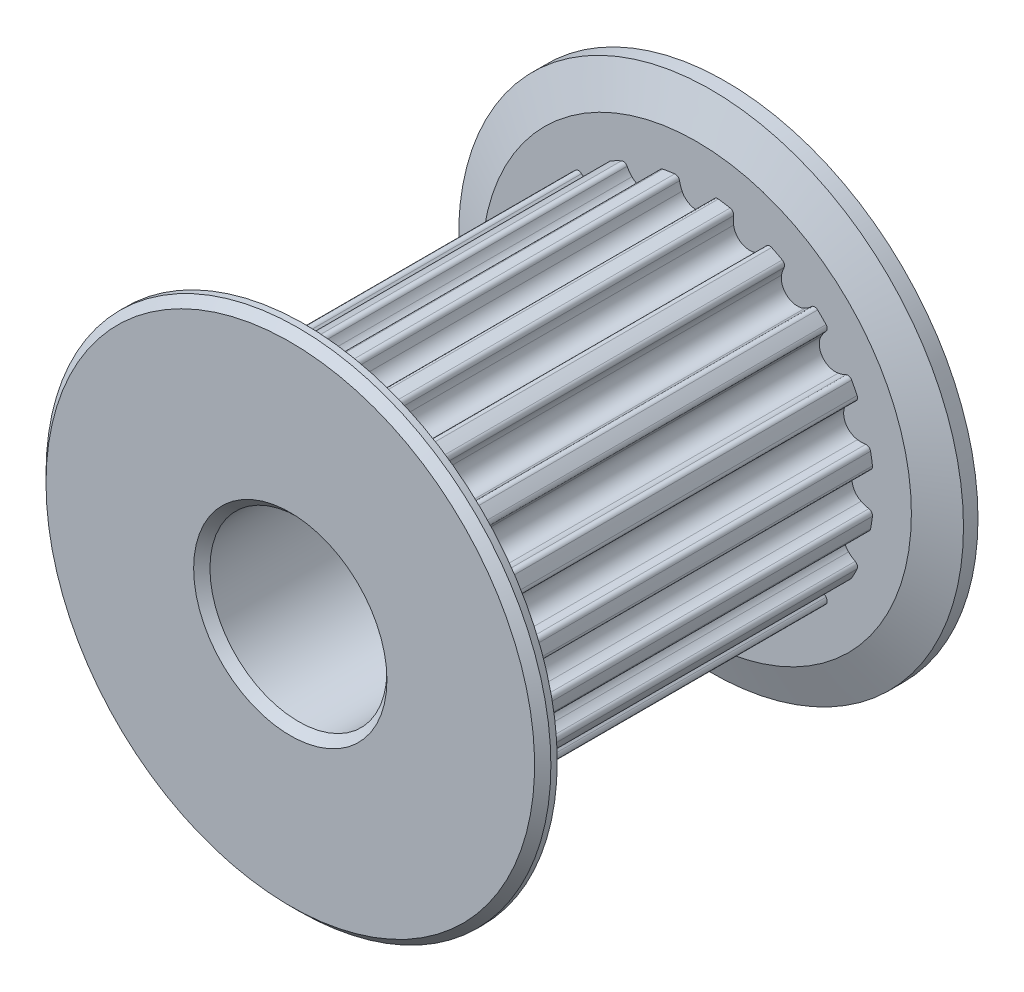
SolidWorks part; units mm, degrees
ref_plane "Front Plane" through (0, 0, 0) normal (0, 0, 1) x (1, 0, 0)
ref_plane "Top Plane" through (0, 0, 0) normal (0, 1, 0) x (1, 0, 0)
ref_plane "Right Plane" through (0, 0, 0) normal (1, 0, 0) x (0, 0, -1)
sketch "Sketch1" plane through (0, 0, 0) normal (0, 0, 1) x (1, 0, 0)
  line L1 (-1.7499, 5.3585) -> (1.7499, 5.3585) construction
  line L4 (0, 0) -> (0, 5.3585) construction
  line L5 (0, 5.3585) -> (0, 11.2107) construction
  line L6 (0, 6.3625) -> (1.9751, 6.0482) construction
  line L7 (1.9751, 6.0482) -> (2.6648, 5.8229) construction
  line L8 (1.9751, 6.0482) -> (1.7499, 5.3585) construction
  line L9 (-1.9751, 6.0482) -> (-1.7499, 5.3585) construction
  line L10 (-1.8963, 5.8067) -> (-2.841, 8.6995)
  line L11 (-2.841, 8.6995) -> (2.841, 8.6995)
  line L12 (2.841, 8.6995) -> (1.8963, 5.8067)
  circle A0 centre (0, 0) radius 6.3625 construction
  circle A1 centre (0, 0) radius 8.6995 construction
  circle A2 centre (0, 0) radius 6.1085 construction
  arc A3 (-0.4989, 5.6703) -> (0.4989, 5.6703) centre (0, 5.9135) ccw
  arc A4 (-0.4989, 5.6703) -> (-0.5855, 5.9387) centre (0.4, 6.1085) cw
  arc A5 (-1.8963, 5.8067) -> (-0.7518, 6.0621) centre (0, 0) cw
  arc A6 (-0.5855, 5.9387) -> (-0.7518, 6.0621) centre (-0.7333, 5.9132) ccw
  arc A7 (1.8963, 5.8067) -> (0.7518, 6.0621) centre (0, 0) ccw
  arc A8 (0.5855, 5.9387) -> (0.7518, 6.0621) centre (0.7333, 5.9132) cw
  arc A9 (0.4989, 5.6703) -> (0.5855, 5.9387) centre (-0.4, 6.1085) ccw
  point P6 (0, 20.9083)
  point P11 (0, 6.3625)
  point P13 (0, 8.6995)
  point P14 (0, 6.1085)
  dimension "D1" = 9.6976
  dimension "PD" = 12.725
  dimension "D2" = 4.8482
  dimension "OD" = 17.399
  dimension "R3" = 0.555
  dimension "R2" = 1
  dimension "R1" = 0.15
  dimension "b" = 0.4
  dimension "D3" = 2
  dimension "PLD" = 0.254
  dimension "h" = 0.75
sketch "Sketch2" plane through (0, 0, 0) normal (1, 0, 0) x (0, 0, -1)
  line L0 (-7.5, 3.05) -> (7.5, 3.05)
  line L1 (-7.5, 3.05) -> (-7.5, 8.6995)
  line L2 (-7, 8.6995) -> (-7.5, 8.6995)
  line L3 (-7.5, 3.05) -> (-7.5, 8.6995) construction
  line L4 (-7.5, 8.6995) -> (-6.5, 8.6995) construction
  line L5 (-6.5, 8.6995) -> (-6.5, 6.1085) construction
  line L6 (-6.5, 6.1085) -> (6.5, 6.1085)
  line L7 (6.5, 6.1085) -> (6.5, 8.6995) construction
  line L8 (6.5, 8.6995) -> (7.5, 8.6995) construction
  line L9 (7.5, 8.6995) -> (7.5, 3.05)
  line L10 (-7.5, 0) -> (7.5, 0) construction
  line L11 (7, 8.6995) -> (6.5, 7.404)
  line L12 (-6.5, 7.404) -> (-7, 8.6995)
  line L14 (-6.5, 7.404) -> (-6.5, 6.1085)
  line L15 (6.5, 6.1085) -> (6.5, 7.404)
  line L16 (7, 8.6995) -> (7.5, 8.6995)
  arc A0 (-6.5, 7.404) -> (-7, 8.6995) centre (-8.4283, 7.404) ccw construction
  arc A1 (6.5, 7.404) -> (7, 8.6995) centre (8.4283, 7.404) cw construction
  point P12 (-6.5, 7.404)
  point P14 (-7, 8.6995)
  point P20 (6.5, 7.404)
  point P21 (7, 8.6995)
  point P25 (6.5, 0)
  point P26 (-6.5, 0)
  dimension "OA" = 15
  dimension "Bore" = 6.1
  dimension "Outside Width" = 14
  dimension "Inside Width" = 13
revolve "Revolve1" add sketch "Sketch2" angle 360 mid plane about L10
sketch "Sketch3" plane through (0, 0, 0) normal (0, 0, 1) x (1, 0, 0)
  line L6 (2.841, 8.6995) -> (-2.841, 8.6995)
  line L7 (1.8963, 5.8067) -> (2.841, 8.6995)
  line L8 (-2.841, 8.6995) -> (-1.8963, 5.8067)
  line L9 (2.841, 8.6995) -> (-2.841, 8.6995)
  line L10 (1.8963, 5.8067) -> (2.841, 8.6995)
  line L11 (-2.841, 8.6995) -> (-1.8963, 5.8067)
  arc A8 (1.8963, 5.8067) -> (0.7518, 6.0621) centre (0, 0) ccw
  arc A9 (0.7518, 6.0621) -> (0.5855, 5.9387) centre (0.7333, 5.9132) ccw
  arc A10 (0.4989, 5.6703) -> (0.5855, 5.9387) centre (-0.4, 6.1085) ccw
  arc A11 (-0.4989, 5.6703) -> (0.4989, 5.6703) centre (0, 5.9135) ccw
  arc A12 (-0.5855, 5.9387) -> (-0.4989, 5.6703) centre (0.4, 6.1085) ccw
  arc A13 (-0.5855, 5.9387) -> (-0.7518, 6.0621) centre (-0.7333, 5.9132) ccw
  arc A14 (-0.7518, 6.0621) -> (-1.8963, 5.8067) centre (0, 0) ccw
  arc A15 (1.8963, 5.8067) -> (0.7518, 6.0621) centre (0, 0) ccw
  arc A16 (0.7518, 6.0621) -> (0.5855, 5.9387) centre (0.7333, 5.9132) ccw
  arc A17 (0.4989, 5.6703) -> (0.5855, 5.9387) centre (-0.4, 6.1085) ccw
  arc A18 (-0.4989, 5.6703) -> (0.4989, 5.6703) centre (0, 5.9135) ccw
  arc A19 (-0.5855, 5.9387) -> (-0.4989, 5.6703) centre (0.4, 6.1085) ccw
  arc A20 (-0.5855, 5.9387) -> (-0.7518, 6.0621) centre (-0.7333, 5.9132) ccw
  arc A21 (-0.7518, 6.0621) -> (-1.8963, 5.8067) centre (0, 0) ccw
  dimension "D1" = 0
extrude "Cut-Extrude1" cut sketch "Sketch3" against normal up to vertex (6.5 mm away) from vertex up to point (0, 6.1085, -6.5) starting at point (0, 6.1085, 6.5)
pattern_circular "CirPattern1" count 20 over 360 about axis through (0, 0, 7.5) along (0, 0, 1) of "Cut-Extrude1"
sketch "Sketch4" plane through (0, 0, 0) normal (1, 0, 0) x (0, -1, 0)
  line L0 (0, -6.5) -> (0, -7.5) construction
  line L1 (-3.05, -7.5) -> (3.05, -7.5) construction
  line L2 (7.404, -6.5) -> (-7.404, -6.5) construction
  circle A0 centre (0, -7) radius 1.7526
  dimension "Set Screw" = 3.5052
ref_plane "Plane1" through (0, 0, 7) normal (0, 0, 1) x (1, 0, 0)
chamfer "Chamfer1" distance 0.2807 angle 45 2 edges at (3.05, 0, 7.5) (8.6995, 0, 7.5)
ref_axis "Center Axis 1" through (0, 0, -7.5) along (0, 0, 1)
ref_plane "Contact Plane 1" through (0, 0, 7.5) normal (0, 0, 1) x (1, 0, 0)
ref_plane "Contact Plane 2" through (0, 0, -7.5) normal (0, 0, -1) x (-1, 0, 0)
sketch "Sketch5" plane through (0, 0, -7.5) normal (0, 0, -1) x (-1, 0, 0)
  line L0 (-1.6733, -2.55) -> (1.6733, -2.55)
  line L1 (-1.6733, -2.55) -> (-1.6733, -3.55)
  line L2 (-1.6733, -3.55) -> (1.6733, -3.55)
  line L3 (1.6733, -3.55) -> (1.6733, -2.55)
  circle A0 centre (0, 0) radius 3.05 construction
  dimension "D1" = 2.55
  dimension "D2" = 1
extrude "Boss-Extrude1" add sketch "Sketch5" against normal blind 9
